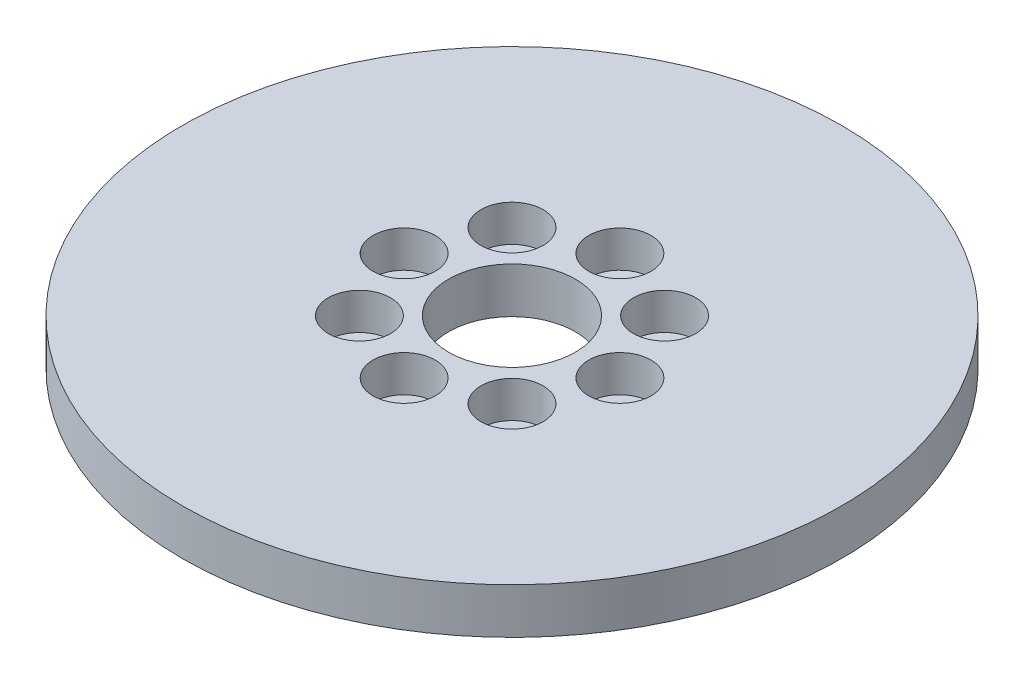
SolidWorks part; units mm, degrees
ref_plane "Front Plane" through (0, 0, 0) normal (0, 0, 1) x (1, 0, 0)
ref_plane "Top Plane" through (0, 0, 0) normal (0, 1, 0) x (1, 0, 0)
ref_plane "Right Plane" through (0, 0, 0) normal (1, 0, 0) x (0, 0, -1)
sketch "Sketch1" plane through (0, 0, 0) normal (0, 1, 0) x (1, 0, 0)
  circle A0 centre (0, 0) radius 65
  dimension "FLANGE_OD" = 130
extrude "Boss-Extrude1" add sketch "Sketch1" along normal blind 9
sketch "Sketch2" plane through (0, 0, 0) normal (0, 1, 0) x (1, 0, 0)
  circle A0 centre (0, 0) radius 12.5
  dimension "BORE_D" = 25
extrude "Cut-Extrude1" cut sketch "Sketch2" along normal through all
sketch "Sketch3" plane through (0, 9, 0) normal (0, 1, 0) x (1, 0, 0)
  circle A0 centre (0, 0) radius 21.2801 construction
  circle A1 centre (-21.2801, 0) radius 6.134
  dimension "BOLT_D" = 12.2681
  dimension "BOLT_PCD" = 42.5601
extrude "Cut-Extrude2" cut sketch "Sketch3" against normal blind 7.2136
pattern_circular "CirPattern1" count 8 over 360 about axis through (0, 0, 0) along (0, 1, 0) of "Cut-Extrude2"
